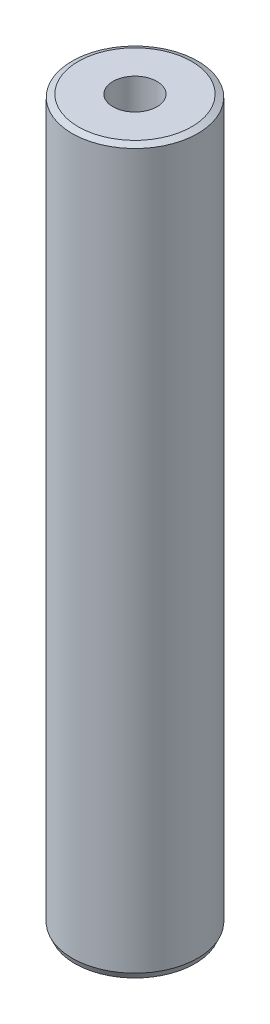
SolidWorks part; units mm, degrees
ref_plane "Front Plane" through (0, 0, 0) normal (0, 0, 1) x (1, 0, 0)
ref_plane "Top Plane" through (0, 0, 0) normal (0, 1, 0) x (1, 0, 0)
ref_plane "Right Plane" through (0, 0, 0) normal (1, 0, 0) x (0, 0, -1)
sketch "Sketch1" plane through (0, 0, 0) normal (0, 1, 0) x (1, 0, 0)
  circle A0 centre (0, 0) radius 12.5
  dimension "SHAFT_OD" = 25
extrude "Boss-Extrude1" add sketch "Sketch1" along normal blind 143.9148
sketch "Sketch2" plane through (0, 0, 0) normal (0, 1, 0) x (1, 0, 0)
  circle A0 centre (0, 0) radius 4.382
  dimension "BORE_D" = 8.7641
extrude "Cut-Extrude1" cut sketch "Sketch2" along normal through all
chamfer "Chamfer1" distance 0.5484 angle 65.701 2 edges at (0, 143.9148, 12.5) (0, 0, 12.5) first distance on face at (0, 143.9148, 12.5) first distance on face at (0, 0, 4.382)
